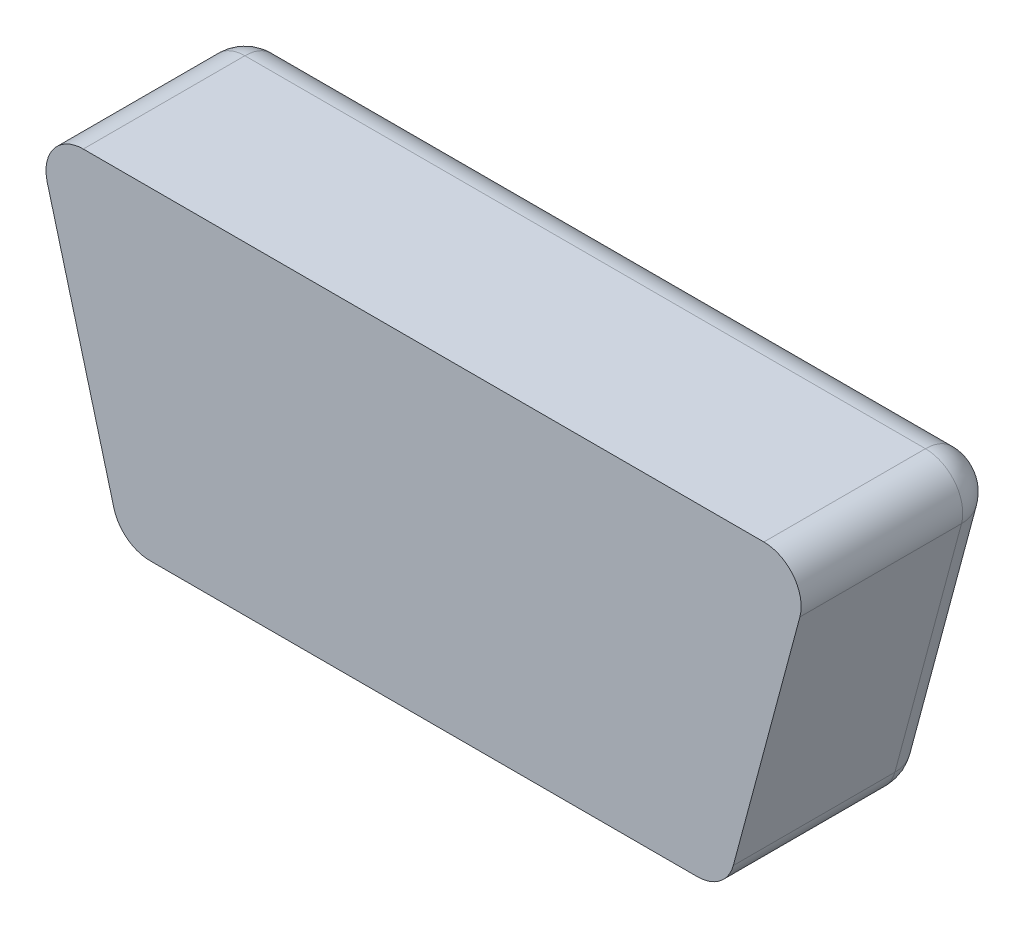
SolidWorks part; units mm, degrees
ref_plane "Спереди" through (0, 0, 0) normal (0, 0, 1) x (1, 0, 0)
ref_plane "Сверху" through (0, 0, 0) normal (0, 1, 0) x (1, 0, 0)
ref_plane "Справа" through (0, 0, 0) normal (1, 0, 0) x (0, 0, -1)
sketch "Эскиз1" plane through (0, 0, 0) normal (0, 0, 1) x (1, 0, 0)
  line L0 (-6.08, -3.25) -> (6.08, -3.25)
  line L1 (6.08, -3.25) -> (7.8217, 3.25)
  line L2 (7.8217, 3.25) -> (-7.8217, 3.25)
  line L3 (-7.8217, 3.25) -> (-6.08, -3.25)
  point P2 (0, -3.25)
  point P5 (0, 3.25)
  point P6 (52.5223, 13.8072)
  point P7 (38.628, 8.0345)
  point P8 (-6.9508, 0)
  point P9 (0, 0)
  point P10 (6.9508, 0)
  dimension "D1" = 12.16
  dimension "D2" = 6.5
  dimension "D3" = 30
extrude "Бобышка-Вытянуть1" add sketch "Эскиз1" along normal blind 4
fillet "Скругление1" radius 0.75 8 edges at (-7.8217, 3.25, 2) (-6.08, -3.25, 2) (-6.9508, 0, 0) (0, -3.25, 0) (6.08, -3.25, 2) (6.9508, 0, 0) (0, 3.25, 0) (7.8217, 3.25, 2)
